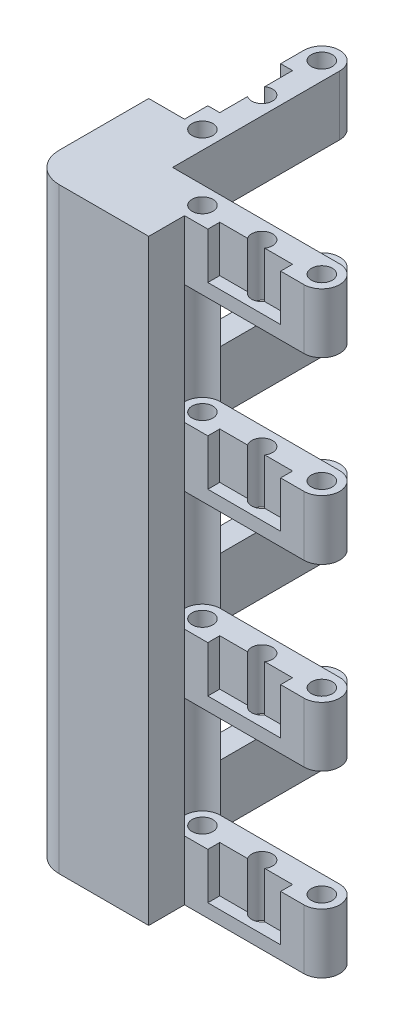
SolidWorks part; units mm, degrees
ref_plane "Front Plane" through (0, 0, 0) normal (0, 0, 1) x (1, 0, 0)
ref_plane "Top Plane" through (0, 0, 0) normal (0, 1, 0) x (1, 0, 0)
ref_plane "Right Plane" through (0, 0, 0) normal (1, 0, 0) x (0, 0, -1)
sketch "Sketch1" plane through (0, 0, 0) normal (0, 1, 0) x (1, 0, 0)
  line L0 (0, 0) -> (0, 20)
  line L1 (0, 20) -> (12, 20)
  line L2 (12, 20) -> (12, 12)
  line L3 (12, 12) -> (20, 12)
  line L4 (20, 12) -> (20, 0)
  line L5 (20, 0) -> (0, 0)
  dimension "D1" = 20
  dimension "D2" = 20
  dimension "D3" = 12
  dimension "D4" = 12
extrude "Boss-Extrude1" add sketch "Sketch1" along normal blind 50 and the other way blind 50
sketch "Sketch2" plane through (0, 0, 0) normal (0, 1, 0) x (1, 0, 0)
  line L0 (9, 40) -> (9, 20) construction
  line L3 (20, 9) -> (40, 9) construction
  line L6 (20, 12) -> (40, 12)
  line L7 (20, 6) -> (40, 6)
  line L8 (0, 20) -> (0, 0) construction
  line L11 (12, 40) -> (12, 20)
  line L12 (6, 40) -> (6, 20)
  line L13 (0, 0) -> (20, 0) construction
  arc A4 (20, 12) -> (20, 6) centre (20, 9) ccw
  arc A5 (40, 6) -> (40, 12) centre (40, 9) ccw
  arc A6 (12, 40) -> (6, 40) centre (9, 40) ccw
  arc A7 (6, 20) -> (12, 20) centre (9, 20) ccw
  point P2 (9, 30)
  point P8 (30, 9)
  dimension "D1" = 30
  dimension "D2" = 6
  dimension "D3" = 30
  dimension "D4" = 6
  dimension "D5" = 20
  dimension "D6" = 20
  dimension "D7" = 9
  dimension "D8" = 9
extrude "Boss-Extrude2" add sketch "Sketch2" along normal blind 50 and the other way blind 50
fillet "Fillet1" radius 5 1 edges at (0, 0, 0)
extrude "Cut-Extrude2" cut sketch "Sketch2<2>" against normal blind 40 and the other way blind 40
sketch "Sketch2<2>" plane through (0, 0, 0) normal (0, 1, 0) x (1, 0, 0) same geometry as "Sketch2"
extrude "Boss-Extrude3" add sketch "Sketch2<3>" along normal blind 20 and the other way blind 20
sketch "Sketch2<3>" plane through (0, 0, 0) normal (0, 1, 0) x (1, 0, 0) same geometry as "Sketch2"
extrude "Cut-Extrude3" cut sketch "Sketch2<4>" against normal blind 10 and the other way blind 10
sketch "Sketch2<4>" plane through (0, 0, 0) normal (0, 1, 0) x (1, 0, 0) same geometry as "Sketch2"
sketch "Sketch3" plane through (0, 50, 0) normal (0, 1, 0) x (1, 0, 0)
  circle A0 centre (9, 40) radius 1.75
  circle A1 centre (9, 20) radius 1.75
  circle A2 centre (20, 9) radius 1.75
  circle A3 centre (40, 9) radius 1.75
  circle A4 centre (30, 9) radius 1.75
  circle A5 centre (9, 30) radius 1.75
  dimension "D1" = 3.5
extrude "Cut-Extrude1" cut sketch "Sketch3" against normal through all
sketch "Sketch4" plane through (0, 0, -6) normal (0, 0, 1) x (1, 0, 0)
  line L0 (20, 40) -> (40, 40) construction
  line L1 (23.9, 47.75) -> (36.1, 47.75)
  line L2 (23.9, 47.75) -> (23.9, 42.25)
  line L3 (23.9, 42.25) -> (36.1, 42.25)
  line L4 (36.1, 47.75) -> (36.1, 42.25)
  line L5 (23.9, 47.75) -> (36.1, 42.25) construction
  line L6 (23.9, 42.25) -> (36.1, 47.75) construction
  line L9 (40, 40) -> (40, 50) construction
  point P0 (30, 45)
  dimension "D1" = 12.2
  dimension "D2" = 5.5
  dimension "D3" = 5
  dimension "D4" = 10
extrude "Cut-Extrude4" cut sketch "Sketch4" against normal blind 2
pattern_linear "LPattern1" count 4 spacing 30 along (0, -1, 0) of "Cut-Extrude4"
sketch "Sketch6" plane through (6, 0, 0) normal (-1, 0, 0) x (0, 0, 1)
  line L0 (-40, 40) -> (-40, 50) construction
  line L1 (-36.1, 47.75) -> (-23.9, 47.75)
  line L2 (-36.1, 47.75) -> (-36.1, 42.25)
  line L3 (-36.1, 42.25) -> (-23.9, 42.25)
  line L4 (-23.9, 47.75) -> (-23.9, 42.25)
  line L5 (-36.1, 47.75) -> (-23.9, 42.25) construction
  line L6 (-36.1, 42.25) -> (-23.9, 47.75) construction
  line L7 (-40, 50) -> (-20, 50) construction
  point P0 (-30, 45)
  dimension "D1" = 12.2
  dimension "D2" = 10
  dimension "D3" = 5.5
  dimension "D4" = 5
extrude "Cut-Extrude5" cut sketch "Sketch6" against normal blind 2
pattern_linear "LPattern2" count 4 spacing 30 along (0, -1, 0) of "Cut-Extrude5"
sketch "Sketch7" plane through (6, 0, 0) normal (-1, 0, 0) x (0, 0, 1)
  line L1 (-36.1, 47.75) -> (-23.9, 47.75)
  line L2 (-36.1, 47.75) -> (-36.1, 51.75)
  line L3 (-36.1, 51.75) -> (-23.9, 51.75)
  line L4 (-23.9, 47.75) -> (-23.9, 51.75)
  dimension "D1" = 4
  dimension "D2" = 12.2
extrude "Cut-Extrude6" cut sketch "Sketch7" against normal blind 2
pattern_linear "LPattern3" count 4 spacing 30 along (0, -1, 0) of "Cut-Extrude6"
sketch "Sketch8" plane through (0, 0, -6) normal (0, 0, 1) x (1, 0, 0)
  line L1 (23.9, 47.75) -> (36.1, 47.75)
  line L2 (23.9, 47.75) -> (23.9, 51.75)
  line L3 (23.9, 51.75) -> (36.1, 51.75)
  line L4 (36.1, 47.75) -> (36.1, 51.75)
  dimension "D1" = 4
  dimension "D2" = 12.2
extrude "Cut-Extrude7" cut sketch "Sketch8" against normal blind 2
pattern_linear "LPattern4" count 4 spacing 30 along (0, -1, 0) of "Cut-Extrude7"
